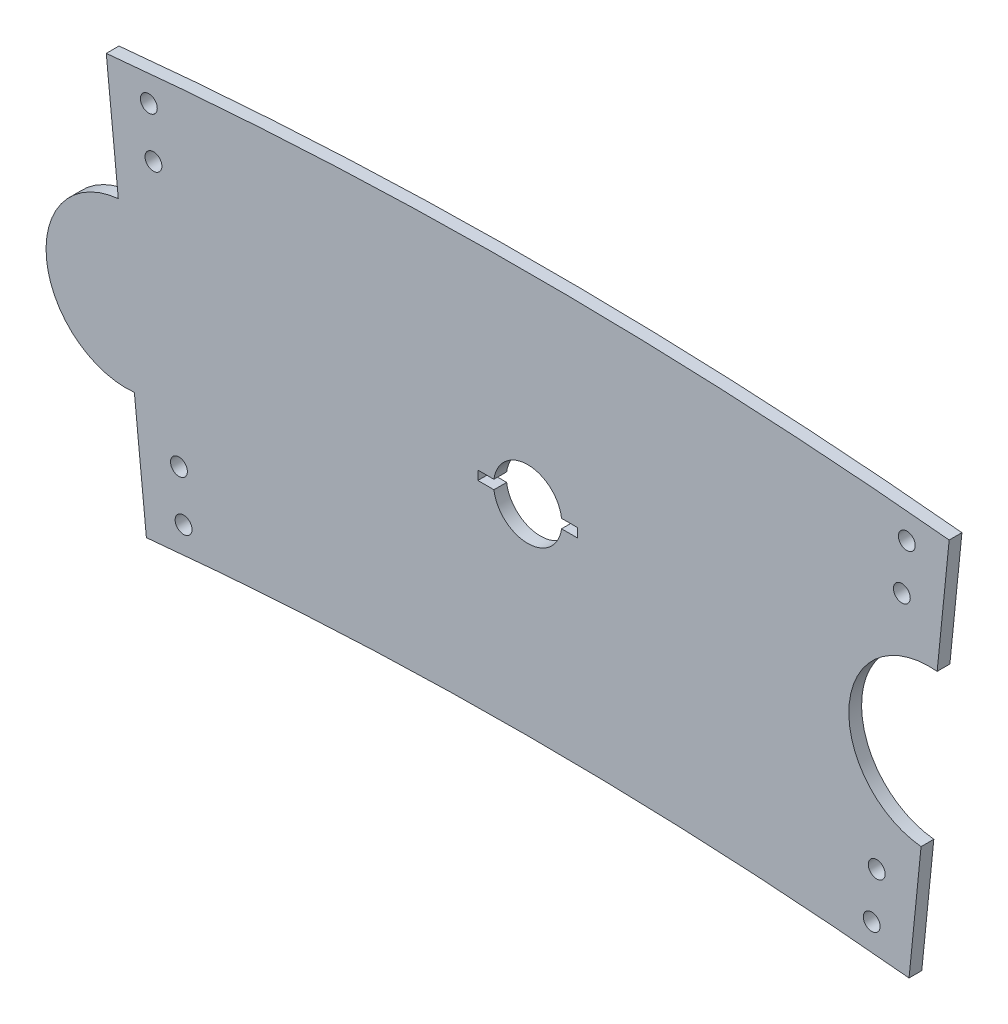
SolidWorks part; units mm, degrees
material "Balsa"
ref_plane "Front Plane" through (0, 0, 0) normal (0, 0, 1) x (1, 0, 0)
ref_plane "Top Plane" through (0, 0, 0) normal (0, 1, 0) x (1, 0, 0)
ref_plane "Right Plane" through (0, 0, 0) normal (1, 0, 0) x (0, 0, -1)
sketch "Sketch1" plane through (0, 0, 0) normal (0, 0, 1) x (1, 0, 0)
  line L0 (8.4252, 1.125) -> (12.4252, 1.125) construction
  line L1 (12.4252, 1.125) -> (12.4252, -1.125) construction
  line L2 (12.4252, -1.125) -> (8.4252, -1.125) construction
  line L3 (-8.4252, -1.125) -> (-12.4252, -1.125) construction
  line L4 (-12.4252, 1.125) -> (-8.4252, 1.125) construction
  line L5 (-12.4252, -1.125) -> (-12.4252, 1.125) construction
  line L6 (-12.4252, 1.125) -> (-8.4252, 1.125)
  line L7 (-12.4252, -1.125) -> (-12.4252, 1.125)
  line L8 (-8.4252, -1.125) -> (-12.4252, -1.125)
  line L9 (12.4252, -1.125) -> (8.4252, -1.125)
  line L10 (12.4252, 1.125) -> (12.4252, -1.125)
  line L11 (8.4252, 1.125) -> (12.4252, 1.125)
  line L12 (-105, 44.7368) -> (-102, 14.8872)
  line L13 (0, 0) -> (0, -1000) construction
  line L14 (0, 0) -> (192.465, 0) construction
  line L15 (105, 44.7368) -> (0, -1000) construction
  line L16 (0, -1000) -> (-105, 44.7368) construction
  line L21 (-95, -54.7619) -> (-98, -24.9123)
  line L22 (95, -54.7619) -> (98, -24.9123)
  line L23 (105, 44.7368) -> (102, 14.8872)
  arc A0 (-8.4252, -1.125) -> (8.4252, -1.125) centre (0, 0) ccw construction
  circle A1 centre (0, 0) radius 100 construction
  arc A3 (8.4252, 1.125) -> (-8.4252, 1.125) centre (0, 0) ccw construction
  arc A4 (8.4252, 1.125) -> (-8.4252, 1.125) centre (0, 0) ccw
  arc A5 (-8.4252, -1.125) -> (8.4252, -1.125) centre (0, 0) ccw
  arc A6 (102, 14.8872) -> (98, -24.9123) centre (100, -5.0126) ccw
  circle A8 centre (0, -1000) radius 1000 construction
  arc A9 (95, -54.7619) -> (-95, -54.7619) centre (0, -1000) ccw
  arc A10 (105, 44.7368) -> (-105, 44.7368) centre (0, -1000) ccw
  arc A11 (-102, 14.8872) -> (-98, -24.9123) centre (-100, -5.0126) ccw
  point P8 (0, 50)
  point P9 (0, -50)
  point P10 (-100, -5.0126)
  point P20 (100, -5.0126)
  dimension "D1" = 200
  dimension "D2" = 2000
  dimension "D4" = 20
  dimension "D3" = 50
extrude "Boss-Extrude1" add sketch "Sketch1" along normal blind 3.175
sketch "Sketch3" plane through (0, 0, 3.175) normal (0, 0, 1) x (1, 0, 0)
  circle A1 centre (-94.3968, 39.2339) radius 2.1
  circle A2 centre (-93.2395, 27.2898) radius 2.1
  circle A3 centre (-86.8968, -35.3902) radius 2.1
  circle A4 centre (-85.7395, -47.3343) radius 2.1
  circle A5 centre (85.704, -47.259) radius 2.1
  circle A6 centre (86.9466, -35.3236) radius 2.1
  circle A7 centre (93.204, 27.365) radius 2.1
  circle A8 centre (94.4466, 39.3005) radius 2.1
  point P2 (-93.2395, 27.2898)
  point P3 (-94.3968, 39.2339)
  point P4 (-85.7395, -47.3343)
  point P5 (-86.8968, -35.3902)
  point P6 (93.204, 27.365)
  point P7 (94.4466, 39.3005)
  point P8 (86.9466, -35.3236)
  point P9 (85.704, -47.259)
extrude "Cut-Extrude1" cut sketch "Sketch3" against normal blind 10
